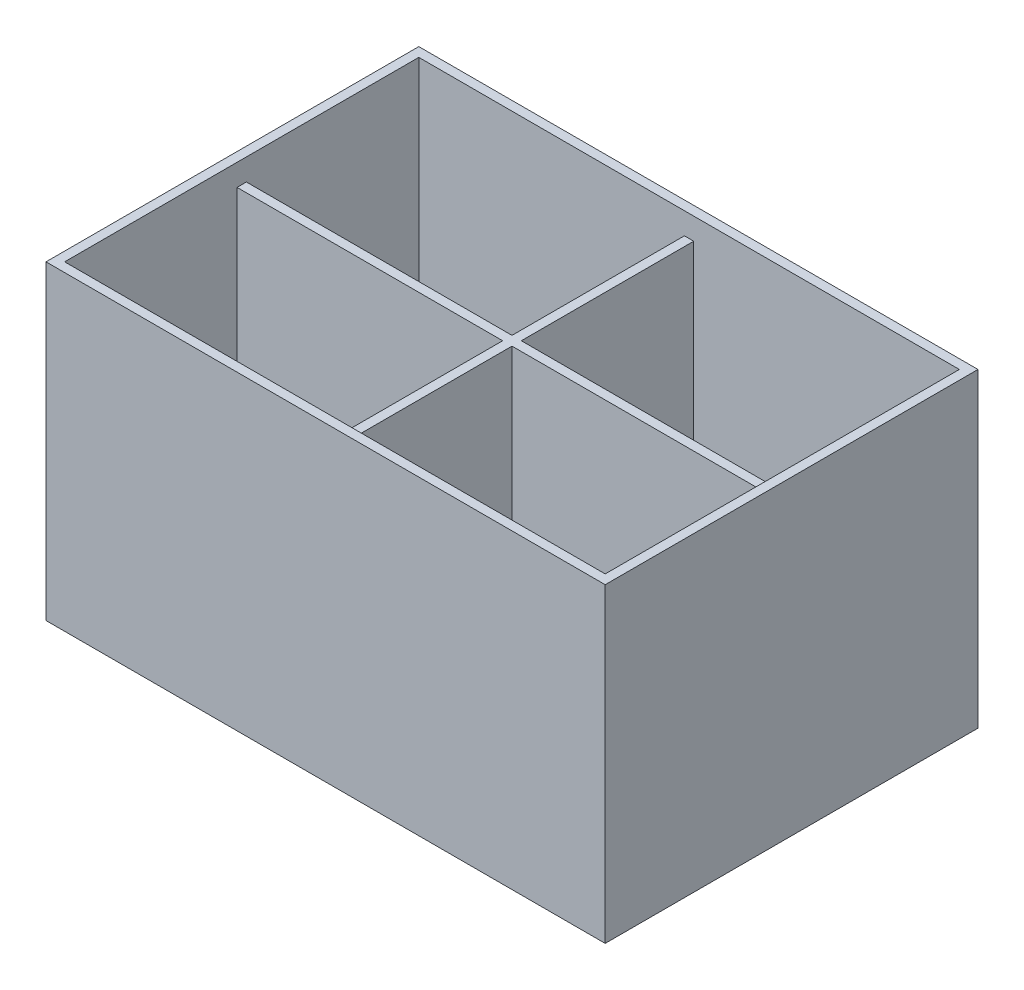
SolidWorks part; units mm, degrees
ref_plane "前视基准面" through (0, 0, 0) normal (0, 0, 1) x (1, 0, 0)
ref_plane "上视基准面" through (0, 0, 0) normal (0, 1, 0) x (1, 0, 0)
ref_plane "右视基准面" through (0, 0, 0) normal (1, 0, 0) x (0, 0, -1)
other "Configuration Table"
sketch "草图1" plane through (0, 0, 0) normal (0, 1, 0) x (1, 0, 0)
  line L0 (-43.5, 28.5) -> (43.5, 28.5)
  line L1 (-45, 30) -> (45, 30)
  line L2 (-45, 30) -> (-45, -30)
  line L3 (-45, -30) -> (45, -30)
  line L4 (45, 30) -> (45, -30)
  line L5 (-45, 30) -> (45, -30) construction
  line L6 (-45, -30) -> (45, 30) construction
  line L7 (43.5, 28.5) -> (43.5, -28.5)
  line L8 (-43.5, -28.5) -> (43.5, -28.5)
  line L9 (-43.5, 28.5) -> (-43.5, -28.5)
  point P0 (0, 0)
  dimension "D1" = 60
  dimension "D2" = 90
  dimension "D3" = 1.5
extrude "凸台-拉伸1" add sketch "草图1" along normal blind 1.5 contours L0 L7 L8 L9
extrude "凸台-拉伸2" add sketch "草图1<3>" along normal blind 50
sketch "草图1<3>" plane through (0, 0, 0) normal (0, 1, 0) x (1, 0, 0) same geometry as "草图1"
sketch "草图2" plane through (0, 1.5, 0) normal (0, 1, 0) x (1, 0, 0)
  line L0 (43.5, -28.5) -> (43.5, 28.5) construction
  line L1 (-43.5, -28.5) -> (43.5, -28.5) construction
  line L2 (-43.5, 28.5) -> (-43.5, -28.5) construction
  line L3 (43.5, 28.5) -> (-43.5, 28.5) construction
  line L4 (43.5, -28.5) -> (43.5, 28.5)
  line L5 (-43.5, -28.5) -> (43.5, -28.5)
  line L6 (-43.5, 28.5) -> (-43.5, -28.5)
  line L7 (43.5, 28.5) -> (-43.5, 28.5)
  line L8 (0, -28.5) -> (0, 28.5) construction
  line L9 (-43.5, 0) -> (43.5, 0) construction
  line L10 (0.75, -28.5) -> (0.75, -0.75)
  line L11 (-43.5, -0.75) -> (-0.75, -0.75)
  line L12 (-0.75, -28.5) -> (-0.75, -0.75)
  line L13 (-43.5, 0.75) -> (-0.75, 0.75)
  line L14 (0.75, 0.75) -> (43.5, 0.75)
  line L15 (-43.5, 0.75) -> (43.5, 0.75) construction
  line L16 (-0.75, 0.75) -> (-0.75, 28.5)
  line L17 (-0.75, -28.5) -> (-0.75, 28.5) construction
  line L18 (0.75, 0.75) -> (0.75, 28.5)
  line L19 (0.75, -28.5) -> (0.75, 28.5) construction
  line L20 (0.75, -0.75) -> (43.5, -0.75)
  line L21 (-43.5, -0.75) -> (43.5, -0.75) construction
  point P7 (0, 0)
  point P12 (0, 0)
  dimension "D1" = 0.75
  dimension "D2" = 0.75
extrude "凸台-拉伸3" add sketch "草图2" along normal blind 45 contours L10 L20 L4 L14 L18 L7 L16 L13 L6 L11 L12 L5 region at (0, 1.5, 0)
